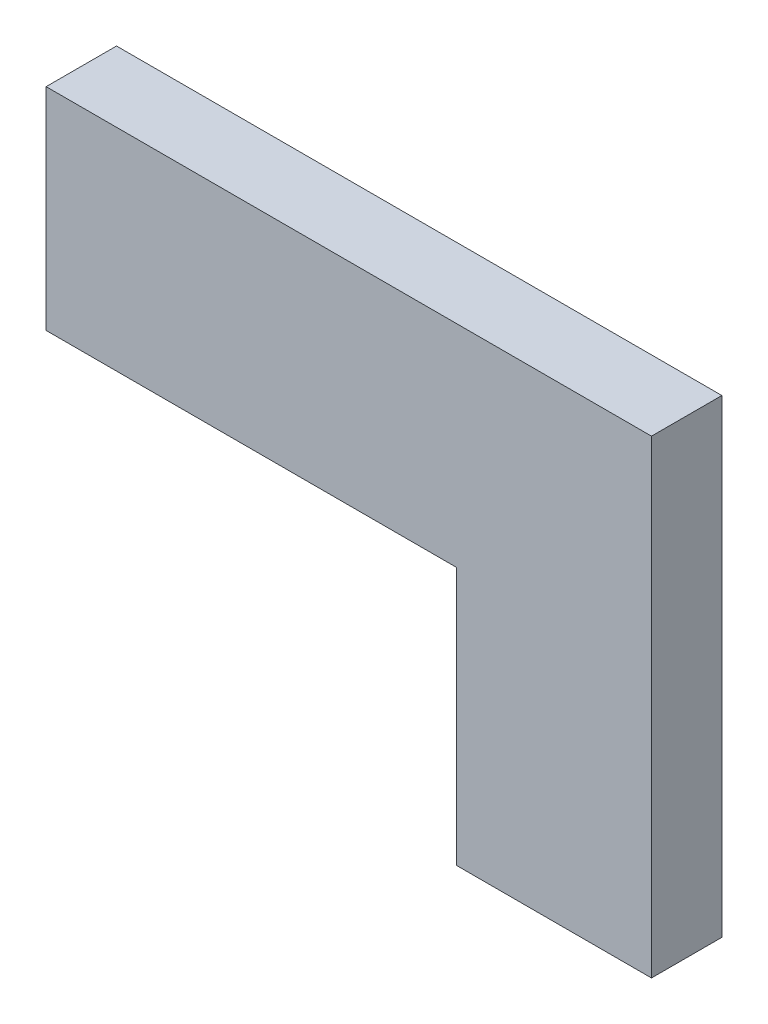
SolidWorks part; units mm, degrees
ref_plane "Front Plane" through (0, 0, 0) normal (0, 0, 1) x (1, 0, 0)
ref_plane "Top Plane" through (0, 0, 0) normal (0, 1, 0) x (1, 0, 0)
ref_plane "Right Plane" through (0, 0, 0) normal (1, 0, 0) x (0, 0, -1)
sketch "Sketch1" plane through (0, 0, 0) normal (0, 0, 1) x (1, 0, 0)
  line L1 (-2.5, 202.5) -> (255.5, 202.5)
  line L2 (-2.5, 202.5) -> (-2.5, 112.5)
  line L3 (-2.5, 112.5) -> (172.5, 112.5)
  line L6 (255.5, 2.5) -> (172.5, 2.5)
  line L7 (255.5, 2.5) -> (255.5, 202.5)
  line L9 (172.5, 2.5) -> (172.5, 112.5)
  dimension "D1" = 110
  dimension "D2" = 175
extrude "Boss-Extrude1" add sketch "Sketch1" along normal up to surface (30 mm away)
equation "\"TubingShort\"= 110mm"
equation "\"D1@Sketch1\"=\"TubingShort\""
equation "\"TubingLong\"= 175mm"
equation "\"D2@Sketch1\"=\"TubingLong\""
equation "\"Length\"= 283mm"
equation "\"Width\"= 225mm"
equation "\"WallThickness\"= 12.5mm"
equation "\"UpperWaterJacketThickness\"= 28mm"
equation "\"SpacerHeight\"= 80.2mm"
equation "\"PlateLength\"= 252mm"
equation "\"PlateWidth\"= 190mm"
equation "\"PlateHoleDiameter\"= 5.9mm"
equation "\"PlateHoleBottom\"= 2mm"
equation "\"PlateHoleSide\"= 1.55mm"
equation "\"PlateHoleSpacing\"= 3.1mm"
equation "\"PlateThickness\"= 1.55mm"
equation "\"ReservoirBottom\"= 12.5mm"
equation "\"ReservoirSupportWidth\"= 12mm"
equation "\"ReservoirSupportHeight\"= 15.1mm"
equation "\"ReservoirSupportPlacementHeight\"= 50mm"
equation "\"ReservoirHoleDiameter\"= 12.7mm"
equation "\"ReservoirHoleRight\"= 25mm"
equation "\"ReservoirHoleTop\"= \"ReservoirSupportPlacementHeight\""
equation "\"ReservoirHeight\"= 90mm"
equation "\"ReservoirPortBottom\"= 4mm"
equation "\"ReservoirPortTop\"= 10mm"
equation "\"ReservoirPortWidth\"= 101mm"
